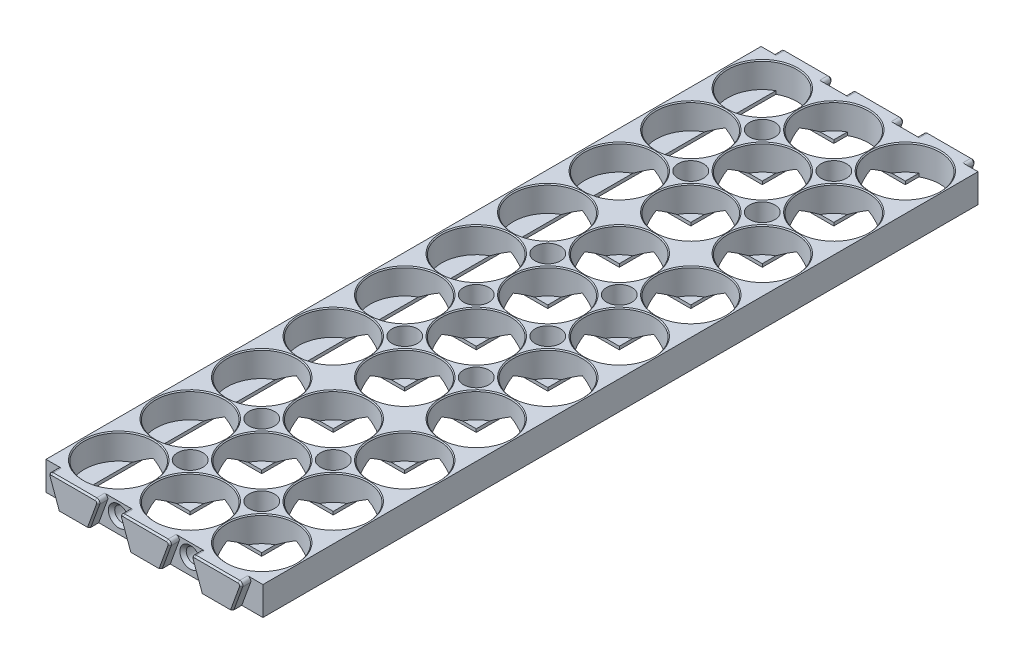
SolidWorks part; units mm, degrees
ref_plane "Front Plane" through (0, 0, 0) normal (0, 0, 1) x (1, 0, 0)
ref_plane "Top Plane" through (0, 0, 0) normal (0, 1, 0) x (1, 0, 0)
ref_plane "Right Plane" through (0, 0, 0) normal (1, 0, 0) x (0, 0, -1)
sketch "Sketch1" plane through (0, 0, 0) normal (0, 1, 0) x (1, 0, 0)
  line L0 (-11.25, 10.875) -> (11.25, 10.875) construction
  line L1 (-11.25, -11.25) -> (11.25, -11.25)
  line L2 (-11.25, -11.25) -> (-11.25, 11.25)
  line L3 (-11.25, 11.25) -> (11.25, 11.25)
  line L4 (11.25, -11.25) -> (11.25, 11.25)
  line L5 (-11.25, -11.25) -> (11.25, 11.25) construction
  line L6 (-11.25, 11.25) -> (11.25, -11.25) construction
  circle A0 centre (0, 0) radius 10.875
  point P0 (0, 0)
  dimension "D1" = 21.75
  dimension "D2" = 22.5
  dimension "D3" = 0.375
extrude "Boss-Extrude1" add sketch "Sketch1" along normal blind 8
sketch "Sketch2" plane through (0, 0, 0) normal (0, -1, 0) x (1, 0, 0)
  line L0 (5.25, 11.25) -> (-5.25, 11.25) construction
  line L1 (11.25, 11.25) -> (5.25, 11.25)
  line L2 (11.25, 11.25) -> (11.25, 5.25)
  line L3 (11.25, 5.25) -> (5.25, 5.25)
  line L4 (5.25, 11.25) -> (5.25, 5.25)
  line L5 (11.25, -11.25) -> (5.25, -11.25)
  line L6 (11.25, -11.25) -> (11.25, -5.25)
  line L7 (11.25, -5.25) -> (5.25, -5.25)
  line L8 (5.25, -11.25) -> (5.25, -5.25)
  line L9 (-11.25, -11.25) -> (-5.25, -11.25)
  line L10 (-11.25, -11.25) -> (-11.25, -5.25)
  line L11 (-11.25, -5.25) -> (-5.25, -5.25)
  line L12 (-5.25, -11.25) -> (-5.25, -5.25)
  line L13 (-11.25, 11.25) -> (-5.25, 11.25)
  line L14 (-11.25, 11.25) -> (-11.25, 5.25)
  line L15 (-11.25, 5.25) -> (-5.25, 5.25)
  line L16 (-5.25, 11.25) -> (-5.25, 5.25)
  line L17 (11.25, 5.25) -> (11.25, -5.25) construction
  line L18 (5.25, -11.25) -> (-5.25, -11.25) construction
  line L19 (-11.25, 5.25) -> (-11.25, -5.25) construction
  dimension "D1" = 10.5
extrude "Boss-Extrude2" add sketch "Sketch2" along normal blind 1
chamfer "Chamfer2" distance 0.3 angle 45 1 edges at (0, 8, 10.875)
pattern_linear "LPattern1" count 10 spacing 22.5 along (0, 0, 1) count 3 spacing 22.5 along (1, 0, 0) of "Boss-Extrude2", "Boss-Extrude1", "Chamfer2"
sketch "Sketch5" plane through (0, 0, -5.25) normal (0, 0, 1) x (1, 0, 0)
  line L25 (-5.25, -1) -> (-5.25, 0) construction
  line L26 (-5.25, -1) -> (-11.25, -1) construction
  line L27 (-11.25, -1) -> (-11.25, 0) construction
  line L29 (-5.25, 0) -> (-9.5238, 0) construction
  line L35 (-5.25, -1) -> (-5.25, 0)
  line L36 (-5.25, -1) -> (-11.25, -1)
  line L37 (-11.25, -1) -> (-11.25, 0)
  line L39 (-5.25, 0) -> (-11.25, 0)
  line L55 (56.25, -1) -> (50.25, -1)
  line L56 (56.25, -1) -> (56.25, 0)
  line L57 (56.25, 0) -> (50.25, 0)
  line L58 (50.25, -1) -> (50.25, 0)
  dimension "D1" = 6
extrude "Boss-Extrude3" add sketch "Sketch5" along normal up to surface (219 mm away)
sketch "Sketch6" plane through (0, 0, 0) normal (0, -1, 0) x (1, 0, 0)
  line L27 (39.75, -11.25) -> (50.25, -11.25) construction
  line L28 (50.25, -11.25) -> (50.25, -9.5238) construction
  line L29 (39.75, -9.5238) -> (39.75, -11.25) construction
  line L30 (17.25, -9.5238) -> (17.25, -11.25) construction
  line L31 (17.25, -11.25) -> (27.75, -11.25) construction
  line L32 (27.75, -11.25) -> (27.75, -9.5238) construction
  line L33 (-5.25, -9.5238) -> (-5.25, -11.25) construction
  line L34 (-5.25, -11.25) -> (5.25, -11.25) construction
  line L35 (5.25, -11.25) -> (5.25, -9.5238) construction
  line L51 (39.75, -11.25) -> (50.25, -11.25)
  line L52 (50.25, -11.25) -> (50.25, -9.5238)
  line L53 (39.75, -9.5238) -> (39.75, -11.25)
  line L54 (17.25, -9.5238) -> (17.25, -11.25)
  line L55 (17.25, -11.25) -> (27.75, -11.25)
  line L56 (27.75, -11.25) -> (27.75, -9.5238)
  line L57 (-5.25, -9.5238) -> (-5.25, -11.25)
  line L58 (-5.25, -11.25) -> (5.25, -11.25)
  line L59 (5.25, -11.25) -> (5.25, -9.5238)
  line L111 (50.25, 212.0238) -> (50.25, 213.75) construction
  line L112 (50.25, 213.75) -> (39.75, 213.75) construction
  line L113 (39.75, 213.75) -> (39.75, 212.0238) construction
  line L114 (27.75, 212.0238) -> (27.75, 213.75) construction
  line L115 (27.75, 213.75) -> (17.25, 213.75) construction
  line L116 (17.25, 213.75) -> (17.25, 212.0238) construction
  line L117 (5.25, 213.75) -> (-5.25, 213.75) construction
  line L118 (-5.25, 213.75) -> (-5.25, 212.0238) construction
  line L119 (5.25, 212.0238) -> (5.25, 213.75) construction
  line L123 (50.25, 212.0238) -> (50.25, 213.75)
  line L124 (50.25, 213.75) -> (39.75, 213.75)
  line L125 (39.75, 213.75) -> (39.75, 212.0238)
  line L126 (27.75, 212.0238) -> (27.75, 213.75)
  line L127 (27.75, 213.75) -> (17.25, 213.75)
  line L128 (17.25, 213.75) -> (17.25, 212.0238)
  line L129 (5.25, 213.75) -> (-5.25, 213.75)
  line L130 (-5.25, 213.75) -> (-5.25, 212.0238)
  line L131 (5.25, 212.0238) -> (5.25, 213.75)
  arc A9 (39.75, -9.5238) -> (50.25, -9.5238) centre (45, 0) ccw construction
  arc A10 (17.25, -9.5238) -> (27.75, -9.5238) centre (22.5, 0) ccw construction
  arc A11 (-5.25, -9.5238) -> (5.25, -9.5238) centre (0, 0) ccw construction
  arc A17 (39.75, -9.5238) -> (50.25, -9.5238) centre (45, 0) ccw
  arc A18 (17.25, -9.5238) -> (27.75, -9.5238) centre (22.5, 0) ccw
  arc A19 (-5.25, -9.5238) -> (5.25, -9.5238) centre (0, 0) ccw
  arc A37 (50.25, 212.0238) -> (39.75, 212.0238) centre (45, 202.5) ccw construction
  arc A38 (27.75, 212.0238) -> (17.25, 212.0238) centre (22.5, 202.5) ccw construction
  arc A39 (5.25, 212.0238) -> (-5.25, 212.0238) centre (0, 202.5) ccw construction
  arc A41 (50.25, 212.0238) -> (39.75, 212.0238) centre (45, 202.5) ccw
  arc A42 (27.75, 212.0238) -> (17.25, 212.0238) centre (22.5, 202.5) ccw
  arc A43 (5.25, 212.0238) -> (-5.25, 212.0238) centre (0, 202.5) ccw
extrude "Boss-Extrude4" add sketch "Sketch6" along normal up to surface (1 mm away) up to face at (-8.25, -1, 101.25)
sketch "Sketch7" plane through (0, 0, 0) normal (0, 0, 1) x (1, 0, 0)
  line L1 (-5.25, 0) -> (5.25, 0)
  line L2 (-5.25, 0) -> (0, 5.25) construction
  line L3 (0, 5.25) -> (5.25, 0) construction
  line L4 (0, 0) -> (0, 8) construction
  line L5 (-11.25, 8) -> (56.25, 8) construction
  line L6 (-5.25, 0) -> (0, 3.0311)
  line L7 (0, 3.0311) -> (5.25, 0)
  line L9 (-5.25, -1) -> (-5.25, 0) construction
  line L10 (5.25, -1) -> (5.25, 0) construction
  line L11 (-5.25, -1) -> (-5.25, 0) construction
  line L12 (5.25, -1) -> (5.25, 0) construction
  line L13 (17.25, 0) -> (22.5, 3.0311)
  line L14 (22.5, 3.0311) -> (27.75, 0)
  line L15 (17.25, 0) -> (27.75, 0)
  line L16 (39.75, 0) -> (45, 3.0311)
  line L17 (45, 3.0311) -> (50.25, 0)
  line L18 (39.75, 0) -> (50.25, 0)
  line L19 (62.25, 0) -> (67.5, 3.0311)
  line L20 (67.5, 3.0311) -> (72.75, 0)
  line L21 (62.25, 0) -> (72.75, 0)
  line L22 (-5.25, 0) -> (17.25, 0) construction
  dimension "D1" = 45
  dimension "D2" = 30
  dimension "D3" = 4.9689
  dimension "D5" = 22.5
  dimension "D4" = 4
extrude "Cut-Extrude1" cut sketch "Sketch7" along normal up to surface (207.75 mm away) up to face at (11.25, -0.3333, 207.75)
sketch "Sketch16" plane through (0, 0, 0) normal (1, 0, 0) x (0, 0, -1)
  line L2 (-5.25, -1) -> (-5.25, 0) construction
  line L3 (5.25, -1) -> (5.25, 0) construction
  line L4 (-5.25, 0) -> (0, 3.0311)
  line L5 (0, 3.0311) -> (5.25, 0)
  line L6 (-5.25, 0) -> (5.25, 0)
  line L7 (-5.25, -1) -> (-5.25, 0) construction
  line L8 (5.25, -1) -> (5.25, 0) construction
  line L9 (-22.5, 3.0311) -> (-17.25, 0)
  line L10 (-27.75, 0) -> (-17.25, 0)
  line L11 (-27.75, 0) -> (-22.5, 3.0311)
  line L12 (-45, 3.0311) -> (-39.75, 0)
  line L13 (-50.25, 0) -> (-39.75, 0)
  line L14 (-50.25, 0) -> (-45, 3.0311)
  line L15 (-67.5, 3.0311) -> (-62.25, 0)
  line L16 (-72.75, 0) -> (-62.25, 0)
  line L17 (-72.75, 0) -> (-67.5, 3.0311)
  line L18 (-90, 3.0311) -> (-84.75, 0)
  line L19 (-95.25, 0) -> (-84.75, 0)
  line L20 (-95.25, 0) -> (-90, 3.0311)
  line L21 (-112.5, 3.0311) -> (-107.25, 0)
  line L22 (-117.75, 0) -> (-107.25, 0)
  line L23 (-117.75, 0) -> (-112.5, 3.0311)
  line L24 (-135, 3.0311) -> (-129.75, 0)
  line L25 (-140.25, 0) -> (-129.75, 0)
  line L26 (-140.25, 0) -> (-135, 3.0311)
  line L27 (-157.5, 3.0311) -> (-152.25, 0)
  line L28 (-162.75, 0) -> (-152.25, 0)
  line L29 (-162.75, 0) -> (-157.5, 3.0311)
  line L30 (-180, 3.0311) -> (-174.75, 0)
  line L31 (-185.25, 0) -> (-174.75, 0)
  line L32 (-185.25, 0) -> (-180, 3.0311)
  line L33 (-202.5, 3.0311) -> (-197.25, 0)
  line L34 (-207.75, 0) -> (-197.25, 0)
  line L35 (-207.75, 0) -> (-202.5, 3.0311)
  line L42 (0, 3.0311) -> (-22.5, 3.0311) construction
  dimension "D1" = 30
  dimension "D3" = 22.5
  dimension "D2" = 10
extrude "Cut-Extrude7" cut sketch "Sketch16" along normal up to surface (39.75 mm away) up to face at (39.75, -0.5, -7.3869)
sketch "Sketch8" plane through (0, 0, -11.25) normal (0, 0, -1) x (-1, 0, 0)
  line L0 (0, -1) -> (0, 8) construction
  line L1 (-27.4743, -1) -> (-30.75, 8)
  line L2 (-56.25, 8) -> (11.25, 8) construction
  line L3 (4.9743, -1) -> (-4.9743, -1)
  line L4 (-4.9743, -1) -> (-8.25, 8)
  line L5 (-8.25, 8) -> (8.25, 8)
  line L6 (4.9743, -1) -> (8.25, 8)
  line L7 (11.25, 8) -> (11.25, -1) construction
  line L8 (11.25, -1) -> (-56.25, -1) construction
  line L9 (-30.75, 8) -> (-14.25, 8)
  line L10 (-56.25, 8) -> (11.25, 8) construction
  line L11 (-17.5257, -1) -> (-14.25, 8)
  line L12 (-17.5257, -1) -> (-27.4743, -1)
  line L13 (-49.9743, -1) -> (-53.25, 8)
  line L14 (-53.25, 8) -> (-36.75, 8)
  line L15 (-40.0257, -1) -> (-36.75, 8)
  line L16 (-40.0257, -1) -> (-49.9743, -1)
  line L21 (-4.9743, -1) -> (-27.4743, -1) construction
  line L22 (-56.25, 8) -> (11.25, 8) construction
  dimension "D1" = 70
  dimension "D2" = 3
  dimension "D4" = 22.5
  dimension "D5" = 9
  dimension "D3" = 3
sketch "Sketch9" plane through (0, 0, 213.75) normal (0, 0, 1) x (1, 0, 0)
  line L24 (-4.9743, -1) -> (4.9743, -1)
  line L25 (4.9743, -1) -> (8.25, 8)
  line L26 (8.25, 8) -> (-8.25, 8)
  line L27 (-8.25, 8) -> (-4.9743, -1)
  line L28 (-4.9743, -1) -> (4.9743, -1)
  line L29 (4.9743, -1) -> (8.25, 8)
  line L30 (8.25, 8) -> (-8.25, 8)
  line L31 (-8.25, 8) -> (-4.9743, -1)
  line L40 (49.9743, -1) -> (53.25, 8)
  line L41 (53.25, 8) -> (36.75, 8)
  line L42 (36.75, 8) -> (40.0257, -1)
  line L43 (40.0257, -1) -> (49.9743, -1)
  line L44 (49.9743, -1) -> (53.25, 8)
  line L45 (53.25, 8) -> (36.75, 8)
  line L46 (36.75, 8) -> (40.0257, -1)
  line L47 (40.0257, -1) -> (49.9743, -1)
  line L48 (14.25, 8) -> (17.5257, -1)
  line L49 (17.5257, -1) -> (27.4743, -1)
  line L50 (27.4743, -1) -> (30.75, 8)
  line L51 (30.75, 8) -> (14.25, 8)
  line L52 (14.25, 8) -> (17.5257, -1)
  line L53 (17.5257, -1) -> (27.4743, -1)
  line L54 (27.4743, -1) -> (30.75, 8)
  line L55 (30.75, 8) -> (14.25, 8)
  dimension "D1" = 0
  dimension "D3" = 0
  dimension "D4" = 0
extrude "Boss-Extrude5" add sketch "Sketch8" along normal blind 3
extrude "Boss-Extrude6" add sketch "Sketch9" along normal blind 3
fillet "Fillet1" radius 1 12 edges at (53.25, 8, -12.75) (36.75, 8, -12.75) (30.75, 8, -12.75) (14.25, 8, -12.75) (8.25, 8, -12.75) (-8.25, 8, -12.75) (-8.25, 8, 215.25) (8.25, 8, 215.25) (14.25, 8, 215.25) (30.75, 8, 215.25) (36.75, 8, 215.25) (53.25, 8, 215.25)
chamfer "Chamfer3" distance 0.5 angle 45 30 edges at (6.3679, 2.829, -14.25) (0, 8, -14.25) (-6.3679, 2.829, -14.25) (51.3679, 2.829, -14.25) (45, 8, -14.25) (38.6321, 2.829, -14.25) (28.8679, 2.829, -14.25) (22.5, 8, -14.25) (16.1321, 2.829, -14.25) (51.3679, 2.829, 216.75) (38.6321, 2.829, 216.75) (45, 8, 216.75) (28.8679, 2.829, 216.75) (16.1321, 2.829, 216.75) (22.5, 8, 216.75) (6.3679, 2.829, 216.75) (-6.3679, 2.829, 216.75) (0, 8, 216.75) (52.641, 7.5736, 216.75) (37.359, 7.5736, 216.75) (30.141, 7.5736, 216.75) (14.859, 7.5736, 216.75) (7.641, 7.5736, 216.75) (-7.641, 7.5736, 216.75) (52.641, 7.5736, -14.25) (37.359, 7.5736, -14.25) (30.141, 7.5736, -14.25) (14.859, 7.5736, -14.25) (7.641, 7.5736, -14.25) (-7.641, 7.5736, -14.25)
sketch "Sketch10" plane through (0, 0, -11.25) normal (0, 0, -1) x (-1, 0, 0)
  line L0 (-11.25, -1) -> (-11.25, 8) construction
  line L1 (-26.9422, -1) -> (-18.0578, -1) construction
  line L2 (-4.9743, -1) -> (-17.5257, -1) construction
  line L3 (-29.3219, 8) -> (-15.6781, 8) construction
  line L4 (-14.25, 8) -> (-8.25, 8) construction
  line L5 (-22.5, 8) -> (-22.5, -1) construction
  circle A0 centre (-11.25, 4) radius 2.25
  circle A1 centre (-33.75, 4) radius 2.25
  dimension "D2" = 4.5
  dimension "D1" = 4
sketch "Sketch11" plane through (0, 0, 213.75) normal (0, 0, 1) x (1, 0, 0)
  circle A0 centre (11.25, 4) radius 2.25 construction
  circle A1 centre (11.25, 4) radius 2.25
  circle A2 centre (33.75, 4) radius 2.25 construction
  circle A3 centre (33.75, 4) radius 2.25
extrude "Cut-Extrude2" cut sketch "Sketch10" against normal blind 5
extrude "Cut-Extrude3" cut sketch "Sketch11" against normal blind 5
chamfer "Chamfer5" distance 1 angle 45 4 edges at (36, 4, -11.25) (9, 4, -11.25) (36, 4, 213.75) (13.5, 4, 213.75)
sketch "Sketch17" plane through (0, -1, 0) normal (0, -1, 0) x (1, 0, 0)
  line L0 (5.25, 5.25) -> (17.25, 17.25) construction
  line L1 (11.25, 11.25) -> (33.75, 11.25) construction
  line L2 (5.25, 185.25) -> (17.25, 197.25) construction
  circle A0 centre (11.25, 11.25) radius 4
  circle A1 centre (33.75, 11.25) radius 4
  circle A33 centre (33.75, 146.25) radius 4 [skipped]
  circle A35 centre (33.75, 168.75) radius 4 [skipped]
  circle A36 centre (33.75, 191.25) radius 4 [skipped]
  circle A38 centre (33.75, 213.75) radius 4 [skipped]
  circle A40 centre (33.75, 236.25) radius 4 [skipped]
  circle A42 centre (11.25, 146.25) radius 4 [skipped]
  circle A43 centre (11.25, 191.25) radius 4 [skipped]
  circle A44 centre (11.25, 213.75) radius 4 [skipped]
  circle A45 centre (11.25, 236.25) radius 4 [skipped]
  circle A47 centre (11.25, 168.75) radius 4 construction
  circle A48 centre (33.75, 123.75) radius 4 [skipped]
  circle A50 centre (11.25, 123.75) radius 4 [skipped]
  circle A57 centre (33.75, 33.75) radius 4 [skipped]
  circle A58 centre (33.75, 56.25) radius 4 [skipped]
  circle A60 centre (33.75, 78.75) radius 4 [skipped]
  circle A62 centre (33.75, 101.25) radius 4 [skipped]
  circle A64 centre (11.25, 56.25) radius 4 [skipped]
  circle A65 centre (11.25, 78.75) radius 4 [skipped]
  circle A66 centre (11.25, 101.25) radius 4 [skipped]
  circle A68 centre (11.25, 33.75) radius 4 construction
  circle A87 centre (11.25, 258.75) radius 4 [skipped]
  circle A88 centre (33.75, 258.75) radius 4 [skipped]
  circle A90 centre (11.25, 281.25) radius 4 [skipped]
  circle A91 centre (33.75, 281.25) radius 4 [skipped]
  circle A93 centre (11.25, 33.75) radius 4
  circle A94 centre (33.75, 33.75) radius 4
  circle A96 centre (11.25, 56.25) radius 4 construction
  circle A97 centre (33.75, 56.25) radius 4 construction
  circle A99 centre (11.25, 78.75) radius 4
  circle A100 centre (33.75, 78.75) radius 4
  circle A102 centre (11.25, 101.25) radius 4
  circle A103 centre (33.75, 101.25) radius 4
  circle A105 centre (11.25, 123.75) radius 4
  circle A106 centre (33.75, 123.75) radius 4
  circle A108 centre (11.25, 146.25) radius 4 construction
  circle A109 centre (33.75, 146.25) radius 4 construction
  circle A111 centre (11.25, 168.75) radius 4
  circle A112 centre (33.75, 168.75) radius 4
  circle A114 centre (11.25, 191.25) radius 4
  circle A115 centre (33.75, 191.25) radius 4
  dimension "D4" = 22.5
  dimension "D5" = 9
  dimension "D1" = 8
  dimension "D3" = 13
extrude "Cut-Extrude8" cut sketch "Sketch17" against normal through all
sketch "Sketch18" plane through (0, -1, 0) normal (0, -1, 0) x (1, 0, 0)
  line L0 (56.25, -11.25) -> (56.25, 213.75) construction
  line L2 (5.25, 140.25) -> (17.25, 152.25) construction
  line L3 (5.25, 50.25) -> (17.25, 62.25) construction
  line L4 (27.75, 50.25) -> (39.75, 62.25) construction
  line L38 (56.25, 101.25) -> (-11.25, 101.25) construction
  line L40 (-11.25, 213.75) -> (-11.25, -11.25) construction
  line L42 (27.75, 140.25) -> (39.75, 152.25) construction
  circle A0 centre (11.25, 56.25) radius 2.1
  circle A4 centre (33.75, 56.25) radius 2.1
  circle A7 centre (33.75, 146.25) radius 2.1
  circle A8 centre (11.25, 146.25) radius 2.1
  dimension "D1" = 4.2
extrude "Cut-Extrude9" cut sketch "Sketch18" against normal blind 4
sketch "Sketch19" plane through (0, -1, 0) normal (0, -1, 0) x (1, 0, 0)
  line L0 (56.25, 101.25) -> (-11.25, 101.25) construction
  line L2 (-11.25, 213.75) -> (-11.25, -11.25) construction
  line L3 (56.25, -11.25) -> (56.25, 213.75) construction
  circle A2 centre (33.75, 146.25) radius 1.7
  circle A3 centre (11.25, 56.25) radius 1.7
  circle A4 centre (11.25, 146.25) radius 1.7
  circle A5 centre (33.75, 56.25) radius 1.7
  dimension "D1" = 3.4
extrude "Cut-Extrude10" cut sketch "Sketch19" against normal offset from surface (7 mm away) 2 up to face at (33.75, 8, 74.75)
chamfer "Chamfer6" distance 1 angle 45 4 edges at (11.25, -1, 144.15) (11.25, -1, 54.15) (33.75, -1, 144.15) (33.75, -1, 54.15)
sketch "Sketch22" plane through (0, 8, 0) normal (0, 1, 0) x (1, 0, 0)
  line L0 (29.3219, -216.75) -> (15.6781, -216.75) construction
  line L1 (-11.25, 11.25) -> (-11.625, 11.25)
  line L2 (-11.25, 11.25) -> (-11.25, -213.75)
  line L3 (-11.25, -213.75) -> (-11.625, -213.75)
  line L4 (-11.625, 11.25) -> (-11.625, -213.75)
  line L5 (22.5, 14.25) -> (22.5, -216.75) construction
  line L7 (15.6781, 14.25) -> (29.3219, 14.25) construction
  line L13 (-11.25, -213.75) -> (-6.8219, -213.75) construction
  line L14 (56.625, 11.25) -> (56.625, -213.75)
  line L15 (56.25, -213.75) -> (56.625, -213.75)
  line L16 (56.25, 11.25) -> (56.25, -213.75)
  line L17 (56.25, 11.25) -> (56.625, 11.25)
  arc A1 (-5.25, 9.5238) -> (-5.25, -9.5238) centre (0, 0) ccw construction
  point P10 (-10.875, 0)
  dimension "D1" = 0.75
  dimension "D2" = 0.375
extrude "Boss-Extrude7" add sketch "Sketch22" against normal up to surface (9 mm away) up to face at (22.5, -1, 101.25)
sketch "Sketch14" plane through (0, -1, 0) normal (0, -1, 0) x (1, 0, 0)
  line L0 (22.5, -14.25) -> (22.5, 216.75) construction
  line L4 (39.75, 129.75) -> (27.75, 129.75) construction
  line L19 (-5.25, 11.25) -> (-11.625, 11.25) construction
  line L30 (26.9422, -14.25) -> (18.0578, -14.25) construction
  line L39 (-5.25, 9.5238) -> (-5.25, 12.9762) construction
  line L40 (-11.625, -11.25) -> (-11.625, 213.75) construction
  line L51 (-6.25, 10.25) -> (-6.25, 12.25)
  line L52 (18.0578, 216.75) -> (26.9422, 216.75) construction
  line L55 (-10.25, 8.7941) -> (-10.25, 13.7059)
  line L56 (-5.25, -9.5238) -> (-5.25, 212.0238) construction
  line L57 (-10.25, 13.7059) -> (-6.25, 12.25)
  line L59 (33.75, 129.75) -> (33.75, 117.75) construction
  line L60 (-5.25, 191.25) -> (-11.625, 191.25) construction
  line L61 (27.75, 117.75) -> (39.75, 117.75) construction
  line L69 (-11.625, 101.25) -> (-5.25, 101.25) construction
  line L70 (-6.25, 100.25) -> (-6.25, 102.25)
  line L71 (-10.25, 98.7941) -> (-10.25, 103.7059)
  line L75 (-10.25, 8.7941) -> (-6.25, 10.25)
  line L76 (-10.25, 103.7059) -> (-6.25, 102.25)
  line L77 (-10.25, 193.7059) -> (-6.25, 192.25)
  line L78 (-10.25, 188.7941) -> (-6.25, 190.25)
  line L79 (-10.25, 193.7059) -> (-10.25, 188.7941)
  line L84 (-6.25, 192.25) -> (-6.25, 190.25)
  line L85 (56.625, 101.25) -> (50.25, 101.25) construction
  line L86 (50.25, 191.25) -> (56.625, 191.25) construction
  line L87 (50.25, 11.25) -> (56.625, 11.25) construction
  line L93 (55.25, 98.7941) -> (51.25, 100.25)
  line L94 (51.25, 192.25) -> (51.25, 190.25)
  line L95 (55.25, 193.7059) -> (55.25, 188.7941)
  line L98 (-10.25, 98.7941) -> (-6.25, 100.25)
  line L100 (55.25, 188.7941) -> (51.25, 190.25)
  line L101 (55.25, 193.7059) -> (51.25, 192.25)
  line L102 (55.25, 103.7059) -> (51.25, 102.25)
  line L103 (55.25, 8.7941) -> (51.25, 10.25)
  line L104 (55.25, 98.7941) -> (55.25, 103.7059)
  line L105 (51.25, 100.25) -> (51.25, 102.25)
  line L106 (55.25, 13.7059) -> (51.25, 12.25)
  line L107 (55.25, 8.7941) -> (55.25, 13.7059)
  line L108 (51.25, 10.25) -> (51.25, 12.25)
  point P17 (-6.25, 11.25)
  point P18 (-10.25, 11.25)
  point P24 (-10.25, 101.25)
  point P25 (-6.25, 101.25)
  point P32 (-10.25, 191.25)
  point P35 (-6.25, 191.25)
  point P56 (51.25, 191.25)
  point P57 (55.25, 191.25)
  point P58 (51.25, 101.25)
  point P59 (55.25, 101.25)
  point P60 (55.25, 11.25)
  point P61 (51.25, 11.25)
  dimension "D1" = 70
  dimension "D2" = 1.375
  dimension "D3" = 4
  dimension "D4" = 1
  dimension "D5" = 70
  dimension "D7" = 1
  dimension "D8" = 4
extrude "Cut-Extrude11" cut sketch "Sketch14" against normal blind 2
chamfer "Chamfer7" distance 0.5 angle 45 24 edges at (-10.25, -1, 191.25) (-8.25, -1, 189.5221) (-6.25, -1, 191.25) (-8.25, -1, 192.9779) (51.25, -1, 191.25) (53.25, -1, 189.5221) (55.25, -1, 191.25) (53.25, -1, 192.9779) (51.25, -1, 101.25) (53.25, -1, 99.5221) (55.25, -1, 101.25) (53.25, -1, 102.9779) (-6.25, -1, 101.25) (-8.25, -1, 99.5221) (-10.25, -1, 101.25) (-8.25, -1, 102.9779) (53.25, -1, 9.5221) (55.25, -1, 11.25) (51.25, -1, 11.25) (53.25, -1, 12.9779) (-6.25, -1, 11.25) (-8.25, -1, 9.5221) (-10.25, -1, 11.25) (-8.25, -1, 12.9779)
equation "\"cell_side\"= 22.50"
equation "\"D2@Sketch1\"=\"cell_side\""
equation "\"D5@Sketch7\"=\"cell_side\""
equation "\"D3@Sketch16\"=\"cell_side\""
equation "\"D4@Sketch8\"=\"cell_side\""
equation "\"D3@LPattern1\"=\"cell_side\""
equation "\"D4@LPattern1\"=\"cell_side\""
equation "\"D4@Sketch17\"=\"cell_side\""
